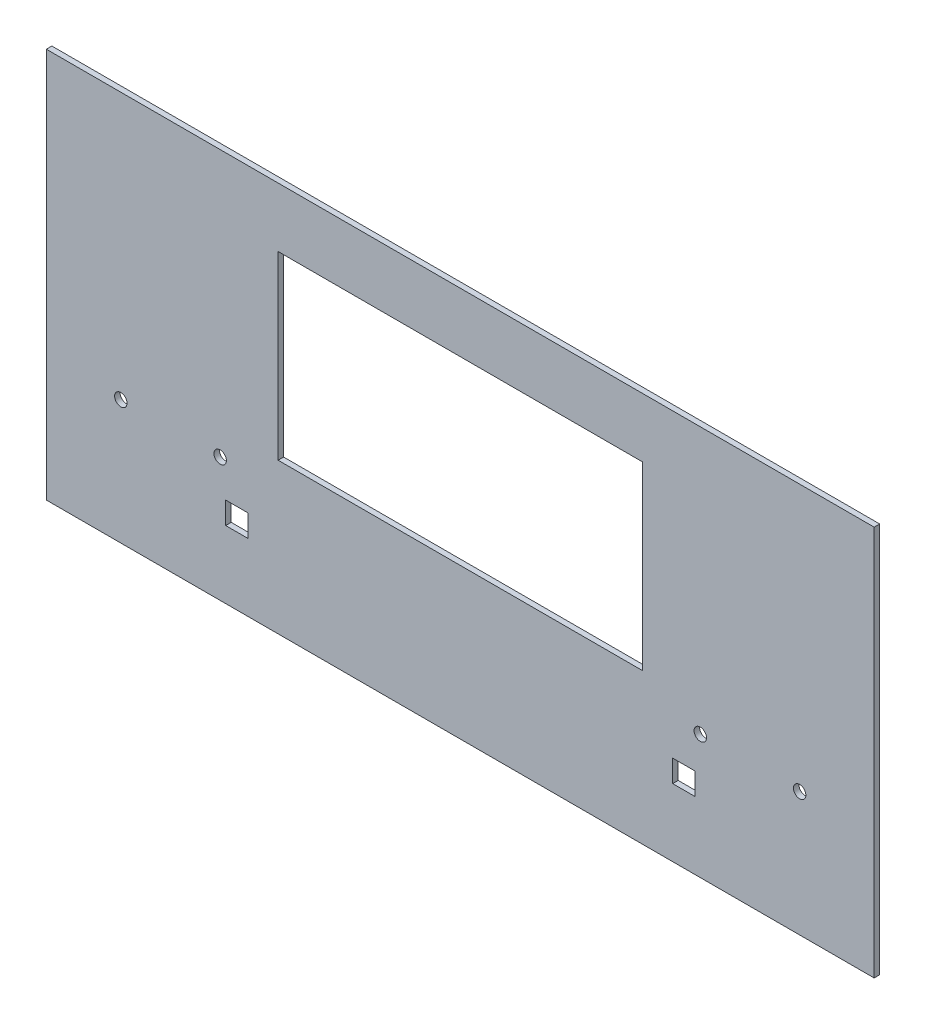
SolidWorks part; units mm, degrees
ref_plane "Front Plane" through (0, 0, 0) normal (0, 0, 1) x (1, 0, 0)
ref_plane "Top Plane" through (0, 0, 0) normal (0, 1, 0) x (1, 0, 0)
ref_plane "Right Plane" through (0, 0, 0) normal (1, 0, 0) x (0, 0, -1)
sketch "SK_Panel" plane through (0, 0, 0) normal (0, 0, 1) x (1, 0, 0)
  line L1 (-150, 0) -> (150, 0)
  line L2 (-150, 0) -> (-150, 141.5)
  line L3 (-150, 141.5) -> (150, 141.5)
  line L4 (150, 0) -> (150, 141.5)
  dimension "D1" = 300
  dimension "D2" = 141.5
  dimension "D3" = 150
extrude "EX_Panel" add sketch "SK_Panel" along normal blind 2
sketch "SK_DrawerOpening" plane through (0, 0, 0) normal (0, 0, 1) x (1, 0, 0)
  line L1 (-66, 54.5) -> (66, 54.5)
  line L2 (-66, 54.5) -> (-66, 120)
  line L3 (-66, 120) -> (66, 120)
  line L4 (66, 54.5) -> (66, 120)
  dimension "D1" = 132
  dimension "D2" = 65.5
  dimension "D3" = 66
  dimension "D4" = 54.5
extrude "CUT_DrawerOpening" cut sketch "SK_DrawerOpening" along normal blind 2
sketch "SK_CliffBolts" plane through (0, 0, 0) normal (0, 0, 1) x (1, 0, 0)
  circle A0 centre (123, 45) radius 2.25
  circle A1 centre (87, 45) radius 2.25
  circle A2 centre (-123, 45) radius 2.25
  circle A3 centre (-87, 45) radius 2.25
  dimension "D3" = 4.5
  dimension "D6" = 4.5
  dimension "D9" = 4.5
  dimension "D12" = 4.5
  dimension "D1" = 123
  dimension "D2" = 45
  dimension "D4" = 87
  dimension "D5" = 45
  dimension "D7" = 123
  dimension "D8" = 45
  dimension "D10" = 87
  dimension "D11" = 45
extrude "CUT_CliffBolts" cut sketch "SK_CliffBolts" along normal blind 2
sketch "SK_CliffCables" plane through (0, 0, 0) normal (0, 0, 1) x (1, 0, 0)
  line L1 (77, 24.5) -> (85, 24.5)
  line L2 (77, 24.5) -> (77, 32.5)
  line L3 (77, 32.5) -> (85, 32.5)
  line L4 (85, 24.5) -> (85, 32.5)
  line L6 (-85, 24.5) -> (-77, 24.5)
  line L7 (-85, 24.5) -> (-85, 32.5)
  line L8 (-85, 32.5) -> (-77, 32.5)
  line L9 (-77, 24.5) -> (-77, 32.5)
  dimension "D1" = 8
  dimension "D2" = 8
  dimension "D3" = 77
  dimension "D4" = 24.5
  dimension "D5" = 8
  dimension "D6" = 8
  dimension "D7" = 85
  dimension "D8" = 24.5
extrude "CUT_CliffCables" cut sketch "SK_CliffCables" along normal blind 2
ref_axis "AX_X" through (0, 0, -0.1) along (0, 0, 1)
ref_axis "AX_Y" through (165, 0, 0) along (-1, 0, 0)
ref_axis "AX_Z" through (0, 148.575, 0) along (0, -1, 0)
equation "\"BODY_L\"= 420"
equation "\"BODY_W\"= 340"
equation "\"FLOOR_Z\"= 35"
equation "\"DECK_Z\"= 180"
equation "\"DECK_T\"= 2"
equation "\"GRID\"= 20"
equation "\"PROFILE\"= 20"
equation "\"SM_T\"= 1.5"
equation "\"PAN_T\"= 1.5"
equation "\"PAN_TOP\"= \"FLOOR_Z\" + \"PAN_T\""
equation "\"RAIL_Y\"= 140"
equation "\"RAIL_X\"= \"BODY_L\" / 2 - \"PROFILE\" / 2 - 2"
equation "\"BOTRING_Z\"= \"PAN_TOP\" + \"PROFILE\" / 2"
equation "\"TOPRING_Z\"= \"DECK_Z\" - \"DECK_T\" - \"PROFILE\" / 2"
equation "\"DRAWER_Z\"= 93"
equation "\"MIDX_Z\"= \"DRAWER_Z\" - \"SM_T\" - \"PROFILE\" / 2"
equation "\"SKIN_Y\"= \"RAIL_Y\" + \"PROFILE\" / 2"
equation "\"SKIN_T\"= 2"
equation "\"WHEEL_D\"= 144"
equation "\"WHEEL_W\"= 52"
equation "\"TRACK\"= 365"
equation "\"AXLE_Z\"= \"WHEEL_D\" / 2"
equation "\"WHEEL_WEB_OFF\"= 6"
equation "\"HUB_T\"= 8"
equation "\"BUSHING_L\"= 6"
equation "\"HUB_GAP\"= 1"
equation "\"MOTOR_UP\"= 7"
equation "\"MOTOR_FACE_Y\"= \"TRACK\" / 2 + \"WHEEL_WEB_OFF\" - (\"BUSHING_L\" + \"HUB_GAP\" + \"HUB_T\")"
equation "\"MOTOR_AXIS_Z\"= \"AXLE_Z\" + \"MOTOR_UP\""
equation "\"CASTER_D\"= 50"
equation "\"CASTER_X\"= 150"
equation "\"CASTER_H\"= 68"
equation "\"POST_X\"= -40"
equation "\"POST_DY\"= 120"
equation "\"POST_SIZE\"= 20"
equation "\"POST_TOP\"= 400"
equation "\"BRACE_Z\"= 335"
equation "\"STRUT_X0\"= -140"
equation "\"HEAD_X0\"= -110"
equation "\"HEAD_X1\"= 12"
equation "\"BEZEL_T\"= 3"
equation "\"WEDGE_MID\"= 7.7"
equation "\"OAK_D\"= 22.9"
equation "\"HEAD_W\"= 210"
equation "\"HEAD_Z0\"= \"POST_TOP\""
equation "\"HEAD_TOP\"= 525"
equation "\"HEAD_TOP_X\"= -20"
equation "\"SCREEN_ANG\"= 35"
equation "\"LENS_X\"= 45.6"
equation "\"LENS_Z\"= 450"
equation "\"OAK_TILT\"= 5"
equation "\"OAK_VFOV_DEPTH\"= 79.5"
equation "\"OAK_VFOV_RGB\"= 72"
equation "\"LIDAR_X\"= 110"
equation "\"SCAN_Z\"= 260"
equation "\"STRUT_Z\"= \"SCAN_Z\" - 20"
equation "\"LIDAR_SCAN_H\"= 27.2"
equation "\"LIDAR_MOUNT_Z\"= \"SCAN_Z\" - \"LIDAR_SCAN_H\""
equation "\"ESTOP_X\"= -172.5"
equation "\"ESTOP_Y\"= -127.5"
equation "\"ESTOP_TOP\"= 225"
equation "\"BUMPER_T\"= 15"
equation "\"BUMPER_Z0\"= 40"
equation "\"BUMPER_Z1\"= 130"
equation "\"CLIFF_X\"= 218"
equation "\"CLIFF_Y\"= 105"
equation "\"CLIFF_Z\"= 72"
equation "\"CLIFF_ANG\"= 50"
equation "\"CONTACT_X\"= 216"
equation "\"CONTACT_Y\"= 64"
equation "\"CONTACT_Z\"= 30"
equation "\"DOCK_TAG_DIST\"= 250"
equation "\"DOCK_TAG_SIZE\"= 80"
equation "\"DOCK_TAG_Z\"= 400"
equation "\"BAT_L\"= 240"
equation "\"BAT_W\"= 90"
equation "\"BAT_H\"= 58"
equation "\"BAT_Z\"= \"DRAWER_Z\" + \"SM_T\""
equation "\"BAT_X\"= 0"
equation "\"PCB_L\"= 95"
equation "\"PCB_W\"= 120"
equation "\"PCB_H\"= 40"
equation "\"PCB_X\"= 62.5"
equation "\"DRV_X\"= 85"
equation "\"DRV_Y\"= 100"
equation "\"DRV_S\"= 50"
equation "\"COMPUTE_X\"= -65"
equation "\"COMPUTE_L\"= 90"
equation "\"COMPUTE_W\"= 160"
equation "\"D1@SK_Panel\" = 2 * (\"RAIL_Y\" + \"PROFILE\" / 2)"
equation "\"D2@SK_Panel\" = \"TOPRING_Z\" + \"PROFILE\" / 2 - \"PAN_TOP\""
equation "\"D3@SK_Panel\" = \"RAIL_Y\" + \"PROFILE\" / 2"
equation "\"D1@EX_Panel\" = \"SKIN_T\""
